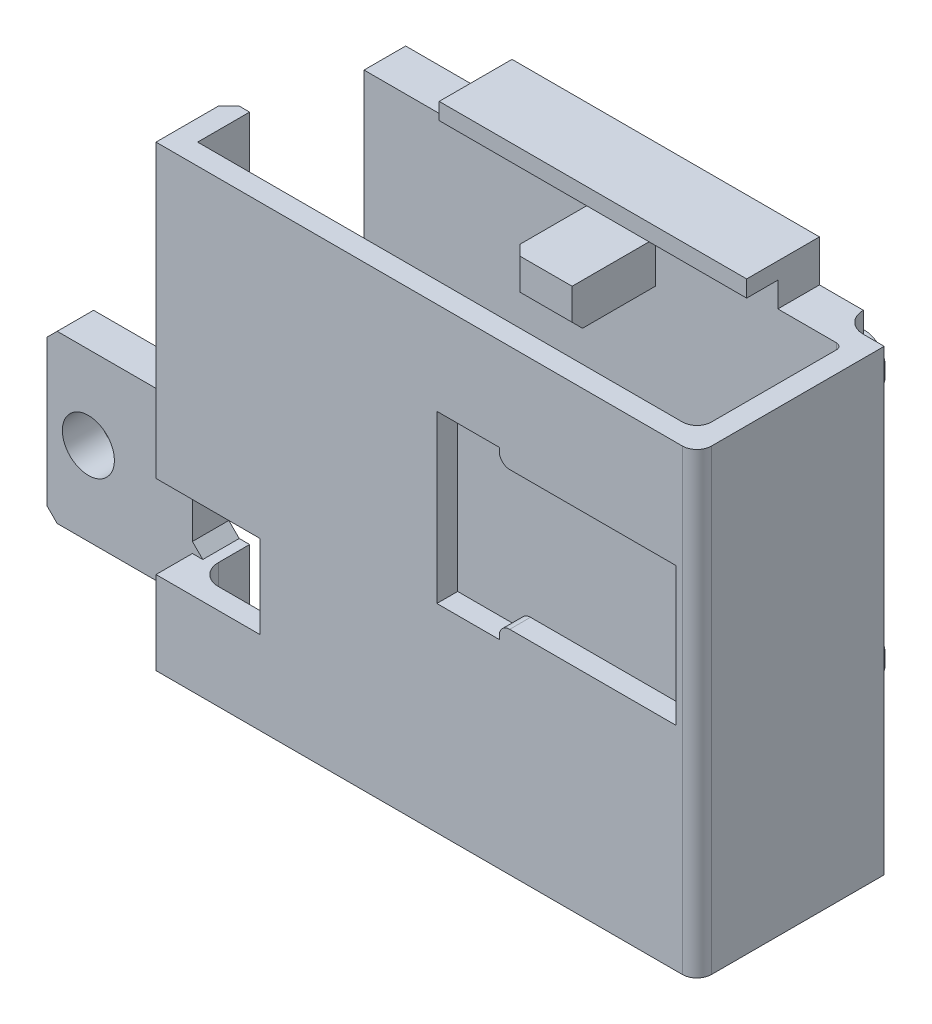
SolidWorks part; units mm, degrees
ref_plane "Front Plane" through (0, 0, 0) normal (1, 0, 0) x (0, 1, 0)
ref_plane "Top Plane" through (0, 0, 0) normal (0, 0, 1) x (0, 1, 0)
ref_plane "Right Plane" through (0, 0, 0) normal (0, 1, 0) x (-1, 0, 0)
sketch "Sketch2" plane through (0, 0, 0) normal (0, 0, 1) x (0, 1, 0)
  line L0 (-7.2, 11.5) -> (-7.2, -11.5)
  line L1 (-7.2, 11.5) -> (7.2, 11.5) construction
  line L2 (-7.2, 11.5) -> (-7.2, -11.5) construction
  line L3 (-7.2, -11.5) -> (7.2, -11.5) construction
  line L4 (7.2, 11.5) -> (7.2, -11.5) construction
  line L5 (-7.2, 11.5) -> (7.2, -11.5) construction
  line L6 (-7.2, -11.5) -> (7.2, 11.5) construction
  line L7 (-7.2, -11.5) -> (-4.8, -11.5)
  line L8 (-7.2, 11.5) -> (-4.8, 11.5)
  line L9 (-4.8, 11.5) -> (-4.8, 5.1)
  line L10 (0, 11.5) -> (0, -11.5) construction
  line L11 (7.2, 11.5) -> (7.2, -11.5) construction
  line L12 (4.8, 11.5) -> (4.8, 5.1)
  line L13 (7.2, 11.5) -> (4.8, 11.5)
  line L14 (7.2, -11.5) -> (4.8, -11.5)
  line L15 (7.2, 11.5) -> (7.2, -11.5)
  line L16 (-4.8, 5.1) -> (4.8, 5.1)
  line L17 (-4.8, -11.5) -> (-4.8, -10)
  line L18 (4.8, -11.5) -> (4.8, -10)
  line L19 (4.8, -10) -> (-4.8, -10)
  point P0 (0, 0)
  dimension "D1" = 14.4
  dimension "D2" = 23
  dimension "D3" = 2.4
  dimension "D4" = 6.4
  dimension "D5" = 1.5
extrude "Boss-Extrude1" add sketch "Sketch2" along normal blind 1
fillet "Fillet2" radius 1 8 edges at (11.5, -7.2, 0.5) (11.5, -4.8, 0.5) (11.5, 4.8, 0.5) (11.5, 7.2, 0.5) (-11.5, 7.2, 0.5) (-11.5, 4.8, 0.5) (-11.5, -7.2, 0.5) (-11.5, -4.8, 0.5)
sketch "Sketch3" plane through (0, 0, 1) normal (0, 0, 1) x (1, 0, 0)
  line L0 (-5.1, 0) -> (10, 0) construction
  line L1 (-5.1, 4.8) -> (-5.1, -4.8) construction
  line L2 (10, -4.8) -> (10, 4.8) construction
  line L4 (-2.55, 3.5) -> (7.45, 3.5)
  line L5 (-2.55, 3.5) -> (-2.55, -3.5)
  line L6 (-2.55, -3.5) -> (7.45, -3.5)
  line L7 (7.45, 3.5) -> (7.45, -3.5)
  line L8 (-2.55, 3.5) -> (7.45, -3.5) construction
  line L9 (-2.55, -3.5) -> (7.45, 3.5) construction
  point P6 (2.45, 0)
  dimension "D1" = 7
  dimension "D2" = 10
extrude "Boss-Extrude2" add sketch "Sketch3" along normal blind 2
sketch "Sketch4" plane through (0, 0, 3) normal (0, 0, 1) x (1, 0, 0)
  line L0 (2.45, 3.5) -> (2.45, -3.5) construction
  line L1 (7.45, 3.5) -> (-2.55, 3.5) construction
  line L2 (-2.55, -3.5) -> (7.45, -3.5) construction
  line L4 (-8.55, 11) -> (13.45, 11)
  line L5 (-8.55, 11) -> (-8.55, -11)
  line L6 (-8.55, -11) -> (13.45, -11)
  line L7 (13.45, 11) -> (13.45, -11)
  line L8 (-8.55, 11) -> (13.45, -11) construction
  line L9 (-8.55, -11) -> (13.45, 11) construction
  point P6 (2.45, 0)
  dimension "D1" = 22
extrude "Boss-Extrude3" add sketch "Sketch4" along normal blind 2
sketch "Sketch5" plane through (13.45, 0, 0) normal (1, 0, 0) x (0, 1, 0)
  line L0 (11, 5) -> (11, 3) construction
  line L1 (-11, 5) -> (11, 5)
  line L2 (-11, 5) -> (-11, 4)
  line L3 (-11, 4) -> (11, 4)
  line L4 (11, 5) -> (11, 4)
extrude "Boss-Extrude4" add sketch "Sketch5" along normal blind 2
sketch "Sketch6" plane through (0, 0, 5) normal (0, 0, 1) x (1, 0, 0)
  line L0 (-8.55, -11) -> (15.45, -11) construction
  line L1 (15.45, 11) -> (14.45, 11)
  line L2 (15.45, 11) -> (15.45, -11)
  line L3 (15.45, -11) -> (14.45, -11)
  line L4 (14.45, 11) -> (14.45, -11)
  dimension "D1" = 1
extrude "Boss-Extrude5" add sketch "Sketch6" along normal blind 7
fillet "Fillet4" radius 1 1 edges at (13.45, 0, 4)
fillet "Fillet5" radius 0.3 1 edges at (14.45, 0, 5)
sketch "Sketch7" plane through (0, 0, 12) normal (0, 0, 1) x (1, 0, 0)
  line L1 (15.45, 11) -> (-10.55, 11)
  line L2 (15.45, 11) -> (15.45, -11)
  line L3 (15.45, -11) -> (-10.55, -11)
  line L4 (-10.55, 11) -> (-10.55, -11)
  dimension "D1" = 26
extrude "Boss-Extrude6" add sketch "Sketch7" along normal blind 1
fillet "Fillet6" radius 0.7 1 edges at (14.45, 0, 12)
sketch "Sketch8" plane through (0, 0, 13) normal (0, 0, 1) x (1, 0, 0)
  line L0 (15.45, -11) -> (15.45, 5.87) construction
  line L1 (15.45, -11) -> (15.45, 11) construction
  line L2 (15.45, 5.87) -> (14.45, 5.87) construction
  line L8 (14.45, 5.87) -> (4.45, 5.87)
  line L9 (14.45, 5.87) -> (14.45, -0.78)
  line L10 (14.45, -0.78) -> (4.45, -0.78)
  line L11 (4.45, 5.87) -> (4.45, -0.78)
  dimension "D1" = 16.87
  dimension "D2" = 1
  dimension "D3" = 10
  dimension "D4" = 6.65
extrude "Cut-Extrude1" cut sketch "Sketch8" against normal blind 2
sketch "Sketch9" plane through (0, 0, 12) normal (0, 0, -1) x (1, 0, 0)
  line L0 (13.75, -11) -> (-10.55, -11) construction
  line L5 (-10.55, 11) -> (-9.55, 11)
  line L6 (-10.55, 11) -> (-10.55, -11)
  line L7 (-10.55, -11) -> (-9.55, -11)
  line L8 (-9.55, 11) -> (-9.55, -11)
  dimension "D1" = 1
extrude "Boss-Extrude7" add sketch "Sketch9" along normal blind 2.5
sketch "Sketch10" plane through (0, 0, 13) normal (0, 0, 1) x (1, 0, 0)
  line L0 (-10.55, -11) -> (-10.55, -5) construction
  line L1 (-10.55, 11) -> (-10.55, -11) construction
  line L2 (-10.55, -3) -> (-10.55, -7)
  line L3 (-10.55, -3) -> (-5.55, -3)
  line L4 (-5.55, -3) -> (-5.55, -7)
  line L5 (-5.55, -7) -> (-10.55, -7)
  point P8 (-10.55, -5)
  dimension "D1" = 6
  dimension "D2" = 4
  dimension "D3" = 5
extrude "Cut-Extrude2" cut sketch "Sketch10" against normal up to next
sketch "Sketch11" plane through (0, 0, 5) normal (0, 0, 1) x (1, 0, 0)
  line L0 (2.45, 11) -> (2.45, 9)
  line L1 (15.45, 11) -> (-10.55, 11) construction
  line L2 (2.45, 9) -> (5.45, 9)
  line L3 (5.45, 9) -> (5.45, 11)
  line L4 (5.45, 11) -> (2.45, 11)
  line L5 (15.45, -11) -> (15.45, 11) construction
  dimension "D1" = 10
  dimension "D2" = 3
  dimension "D3" = 2
extrude "Boss-Extrude8" add sketch "Sketch11" along normal blind 4
sketch "Sketch12" plane through (0, 0, 13) normal (0, 0, 1) x (1, 0, 0)
  line L0 (4.45, 5.87) -> (4.45, -0.78) construction
  line L1 (2.95, 6.545) -> (5.95, 6.545)
  line L2 (2.95, 6.545) -> (2.95, -1.455)
  line L3 (2.95, -1.455) -> (5.95, -1.455)
  line L4 (5.95, 6.545) -> (5.95, -1.455)
  line L5 (2.95, 6.545) -> (5.95, -1.455) construction
  line L6 (2.95, -1.455) -> (5.95, 6.545) construction
  point P0 (4.45, 2.545)
  dimension "D1" = 3
  dimension "D2" = 8
extrude "Cut-Extrude3" cut sketch "Sketch12" against normal up to next contours L1 L4 L3 L2
fillet "Fillet7" radius 0.5 1 edges at (5.95, 5.87, 12.5)
fillet "Fillet8" radius 0.5 1 edges at (5.95, -0.78, 12.5)
sketch "Sketch13" plane through (0, -11, 0) normal (0, -1, 0) x (1, 0, 0)
  line L0 (3.95, 5) -> (3.95, 3) construction
  line L1 (2.45, 5) -> (5.45, 5) construction
  line L2 (-8.55, 3) -> (13.45, 3) construction
  line L4 (-3.4393, 5) -> (11.3393, 5)
  line L5 (-3.4393, 5) -> (-3.4393, 3)
  line L6 (-3.4393, 3) -> (11.3393, 3)
  line L7 (11.3393, 5) -> (11.3393, 3)
  line L8 (-3.4393, 5) -> (11.3393, 3) construction
  line L9 (-3.4393, 3) -> (11.3393, 5) construction
  point P6 (3.95, 4)
extrude "Boss-Extrude9" add sketch "Sketch13" along normal blind 2
sketch "Sketch14" plane through (0, 0, 5) normal (0, 0, 1) x (1, 0, 0)
  line L0 (11.3393, -13) -> (11.3393, -11) construction
  line L1 (-3.4393, -13) -> (11.3393, -13)
  line L2 (-3.4393, -13) -> (-3.4393, -12.2)
  line L3 (-3.4393, -12.2) -> (11.3393, -12.2)
  line L4 (11.3393, -13) -> (11.3393, -12.2)
  dimension "D1" = 0.8
extrude "Boss-Extrude10" add sketch "Sketch14" along normal blind 1.5
mirror "Mirror1" about plane through (0, 0, 0) normal (0, 1, 0) of "Boss-Extrude10", "Boss-Extrude9"
fillet "Fillet9" radius 0.7 1 edges at (15.45, 0, 13)
chamfer "Chamfer3" distance 0.5 angle 45 1 edges at (3.95, -13, 6.5)
chamfer "Chamfer4" distance 0.5 angle 45 5 edges at (12.7446, -11, 5) (14.3621, -11, 5.0879) (14.45, -11, 8.3) (14.245, -11, 11.795) (2.1, -11, 12)
fillet "Fillet10" radius 1 1 edges at (-9.55, -8.75, 12)
sketch "Sketch27" plane through (-10.55, 0, 0) normal (-1, 0, 0) x (0, -1, 0)
  line L0 (3, 11.25) -> (7, 11.25) construction
  line L1 (3, 9.5) -> (3, 13) construction
  line L2 (7, 9.5) -> (7, 13) construction
  line L3 (3, 11.25) -> (1, 11.25)
  line L4 (1, 11.25) -> (1, 9.5)
  line L5 (3, 9.5) -> (-11, 9.5) construction
  line L6 (1, 9.5) -> (9, 9.5)
  line L7 (11, 9.5) -> (7, 9.5) construction
  line L8 (9, 9.5) -> (9, 11.25)
  line L9 (9, 11.25) -> (7, 11.25)
  line L10 (3, 11.25) -> (7, 11.25)
  dimension "D1" = 8
extrude "Boss-Extrude14" add sketch "Sketch27" along normal blind 7
chamfer "Chamfer5" distance 0.5 angle 45 2 edges at (-10.55, -7, 10.375) (-10.55, -3, 10.375)
sketch "Sketch28" plane through (0, 0, 11.25) normal (0, 0, 1) x (1, 0, 0)
  line L0 (-17.55, -5) -> (-15.55, -5) construction
  line L1 (-17.55, -9) -> (-17.55, -1) construction
  circle A0 centre (-15.55, -5) radius 1.25
  dimension "D2" = 2.5
  dimension "D1" = 2
extrude "Cut-Extrude5" cut sketch "Sketch28" against normal through all
sketch "Sketch29" plane through (-8.55, 0, 0) normal (-1, 0, 0) x (0, -1, 0)
  line L0 (1, 9.5) -> (1, 3) construction
  line L1 (-3.5, 3) -> (3.5, 3) construction
  line L2 (9, 9.5) -> (9, 3) construction
  line L3 (-11, 3) -> (11, 3) construction
  line L4 (-11, 5) -> (11, 5) construction
  line L5 (1, 3) -> (9, 3)
  line L6 (1, 3) -> (1, 5)
  line L7 (1, 5) -> (9, 5)
  line L8 (9, 3) -> (9, 5)
extrude "Boss-Extrude15" add sketch "Sketch29" along normal up to surface (9 mm away) up to face at (-17.55, -5, 10.375)
sketch "Sketch30" plane through (0, 0, 3) normal (0, 0, -1) x (1, 0, 0)
  circle A0 centre (-15.55, 5) radius 1.25
extrude "Cut-Extrude6" cut sketch "Sketch30" against normal through all
sketch "Sketch31" plane through (0, 0, 5) normal (0, 0, 1) x (1, 0, 0)
  line L0 (-9.55, -7) -> (-9.55, -9.5) construction
  line L1 (-10.55, -1) -> (-9.55, -1)
  line L2 (-10.55, -1) -> (-10.55, -9)
  line L3 (-10.55, -9) -> (-9.55, -9)
  line L4 (-9.55, -1) -> (-9.55, -9)
  line L5 (-17.55, -9) -> (-8.55, -9) construction
extrude "Boss-Extrude16" add sketch "Sketch31" along normal blind 1
chamfer "Chamfer6" distance 0.5 angle 45 1 edges at (-10.55, -5, 6)
chamfer "Chamfer7" distance 0.5 angle 45 1 edges at (-10.55, 5, 9.5)
chamfer "Chamfer8" distance 0.5 angle 45 2 edges at (2.45, 10, 9) (3.95, 9, 9)
chamfer "Chamfer9" distance 0.5 angle 45 1 edges at (-10.05, -11, 9.5)
chamfer "Chamfer10" distance 0.5 angle 45 8 edges at (-8.55, -1, 4) (-17.55, -1, 4) (-17.55, -9, 4) (-8.55, -9, 4) (-10.55, -9, 10.375) (-10.55, -1, 10.625) (-17.55, -1, 10.375) (-17.55, -9, 10.375)
